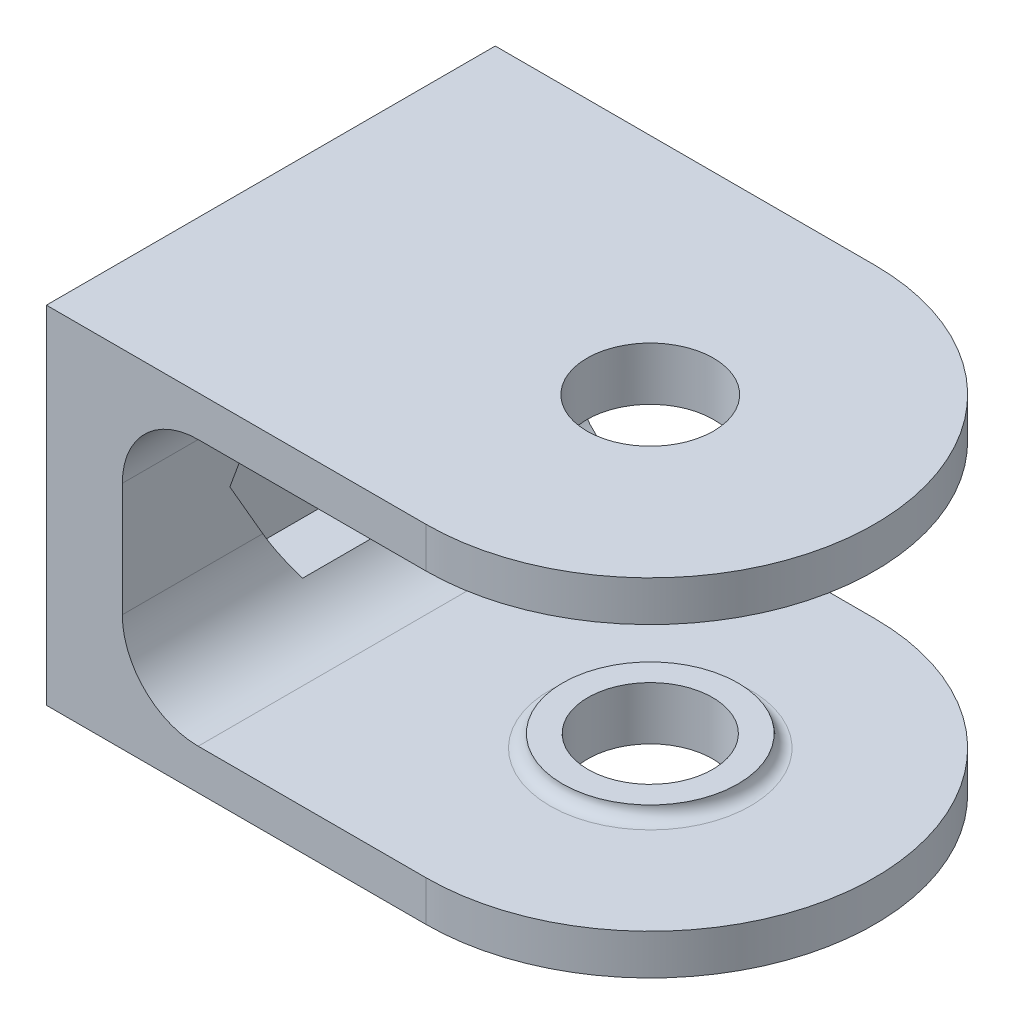
SolidWorks part; units mm, degrees
ref_plane "Front Plane" through (0, 0, 0) normal (0, 0, 1) x (1, 0, 0)
ref_plane "Top Plane" through (0, 0, 0) normal (0, 1, 0) x (1, 0, 0)
ref_plane "Right Plane" through (0, 0, 0) normal (1, 0, 0) x (0, 0, -1)
sketch "Sketch1" plane through (0, 0, 0) normal (0, 1, 0) x (1, 0, 0)
  line L0 (0, 8.872) -> (-15, 8.872)
  line L1 (-15, 8.872) -> (-15, -8.872)
  line L2 (-15, -8.872) -> (0, -8.872)
  arc A0 (0, -8.872) -> (0, 8.872) centre (0, 0) ccw
  circle A1 centre (0, 0) radius 2.4645
  dimension "D1" = 15
extrude "Boss-Extrude1" add sketch "Sketch1" along normal blind 1.6
sketch "Sketch2" plane through (0, 1.6, 0) normal (0, 1, 0) x (1, 0, 0)
  line L0 (-15, -8.872) -> (0, -8.872) construction
  line L1 (-15, 8.872) -> (-12, 8.872)
  line L2 (-15, 8.872) -> (-15, -8.872)
  line L3 (-15, -8.872) -> (-12, -8.872)
  line L4 (-12, 8.872) -> (-12, -8.872)
  dimension "D1" = 3
extrude "Boss-Extrude2" add sketch "Sketch2" along normal blind 10.5
sketch "Sketch3" plane through (0, 12.1, 0) normal (0, 1, 0) x (1, 0, 0)
  line L0 (-15, 8.872) -> (0, 8.872)
  line L1 (0, -8.872) -> (-15, -8.872)
  line L2 (-15, -8.872) -> (-15, 8.872)
  arc A0 (0, 8.872) -> (0, -8.872) centre (0, 0) cw
  circle A1 centre (0, 0) radius 2.5
  dimension "D1" = 5
extrude "Boss-Extrude3" add sketch "Sketch3" along normal blind 1.6
sketch "Sketch4" plane through (-15, 0, 0) normal (-1, 0, 0) x (0, 0, 1)
  line L0 (-8.872, 0) -> (8.872, 13.7) construction
  circle A0 centre (0, 6.85) radius 2.5
extrude "Cut-Extrude1" cut sketch "Sketch4" against normal blind 15.6
sketch "Sketch5" plane through (-12, 0, 0) normal (1, 0, 0) x (0, 0, -1)
  line L1 (4.6188, 6.85) -> (2.3094, 10.85)
  line L2 (2.3094, 10.85) -> (-2.3094, 10.85)
  line L3 (-2.3094, 10.85) -> (-4.6188, 6.85)
  line L4 (-4.6188, 6.85) -> (-2.3094, 2.85)
  line L5 (-2.3094, 2.85) -> (2.3094, 2.85)
  line L6 (2.3094, 2.85) -> (4.6188, 6.85)
  circle A0 centre (0, 6.85) radius 4 construction
  dimension "D1" = 8
extrude "Cut-Extrude2" cut sketch "Sketch5" against normal blind 1.5
fillet "Fillet1" radius 3 2 edges at (-12, 1.6, 0) (-12, 12.1, 0)
sketch "Sketch6" plane through (0, 12.1, 0) normal (0, -1, 0) x (-1, 0, 0)
  circle A0 centre (0, 0) radius 2.5
extrude "Extrude-Thin1" add sketch "Sketch6" along normal blind 0.5 thin thin type one direction wall 1
fillet "Fillet2" radius 0.5 1 edges at (-3.5, 12.1, 0)
sketch "Sketch7" plane through (0, 1.6, 0) normal (0, 1, 0) x (1, 0, 0)
  circle A0 centre (0, 0) radius 2.4645
extrude "Extrude-Thin2" add sketch "Sketch7" along normal blind 0.5 thin thin type one direction wall 1
fillet "Fillet3" radius 0.5 1 edges at (3.4645, 1.6, 0)
